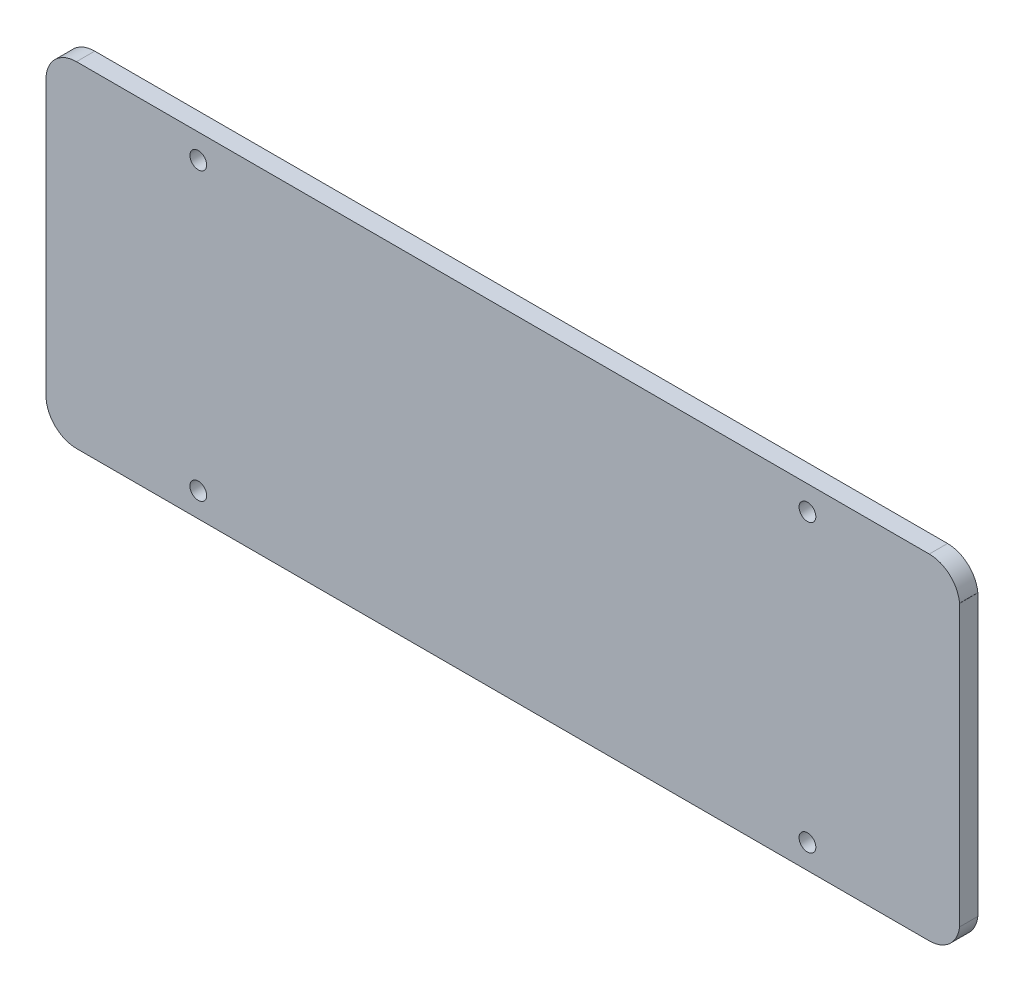
SolidWorks part; units mm, degrees
material "Aircraft Ply"
ref_plane "Front Plane" through (0, 0, 0) normal (0, 0, 1) x (1, 0, 0)
ref_plane "Top Plane" through (0, 0, 0) normal (0, 1, 0) x (1, 0, 0)
ref_plane "Right Plane" through (0, 0, 0) normal (1, 0, 0) x (0, 0, -1)
sketch "Sketch1" plane through (0, 0, 0) normal (0, 0, 1) x (1, 0, 0)
  line L0 (-75, 8) -> (75, 8) construction
  line L1 (-75, 0) -> (75, 0) construction
  line L8 (-75, 23) -> (-75, -23)
  line L9 (-44.3417, -23) -> (-25.6583, -23)
  line L10 (-14.3417, -23) -> (14.3417, -23)
  line L11 (25.6583, -23) -> (44.3417, -23)
  line L12 (75, -23) -> (75, 23)
  line L13 (44.3417, 23) -> (25.6583, 23)
  line L14 (14.3417, 23) -> (-14.3417, 23)
  line L15 (-25.6583, 23) -> (-44.3417, 23)
  line L16 (-75, 23) -> (-75, -23)
  line L17 (-44.3417, -23) -> (-25.6583, -23)
  line L18 (-14.3417, -23) -> (14.3417, -23)
  line L19 (25.6583, -23) -> (44.3417, -23)
  line L20 (75, -23) -> (75, 23)
  line L21 (44.3417, 23) -> (25.6583, 23)
  line L22 (14.3417, 23) -> (-14.3417, 23)
  line L23 (-25.6583, 23) -> (-44.3417, 23)
  line L30 (-75, -23) -> (-55.6583, -23)
  line L31 (-75, -23) -> (-55.6583, -23)
  line L32 (55.6583, -23) -> (75, -23)
  line L33 (55.6583, -23) -> (75, -23)
  line L34 (75, 23) -> (55.6583, 23)
  line L35 (75, 23) -> (55.6583, 23)
  line L36 (-55.6583, 23) -> (-75, 23)
  line L37 (-55.6583, 23) -> (-75, 23)
  line L38 (-54.075, 10.201) -> (-54.075, 5.799)
  line L39 (-61.925, 10.201) -> (-61.925, 5.799)
  line L40 (-29.925, 10.201) -> (-29.925, 5.799)
  line L41 (-22.075, 10.201) -> (-22.075, 5.799)
  line L42 (2.075, 10.201) -> (2.075, 5.799)
  line L43 (9.925, 10.201) -> (9.925, 5.799)
  line L44 (34.075, 10.201) -> (34.075, 5.799)
  line L45 (41.925, 10.201) -> (41.925, 5.799)
  line L46 (-13.925, -5.799) -> (-13.925, -10.201)
  line L47 (-6.075, -5.799) -> (-6.075, -10.201)
  line L48 (18.075, -5.799) -> (18.075, -10.201)
  line L49 (25.925, -5.799) -> (25.925, -10.201)
  line L50 (50.075, -5.799) -> (50.075, -10.201)
  line L51 (57.925, -5.799) -> (57.925, -10.201)
  line L52 (-45.925, -5.799) -> (-45.925, -10.201)
  line L53 (-38.075, -5.799) -> (-38.075, -10.201)
  circle A0 centre (-50, 23.5) radius 1.375 construction
  circle A1 centre (-20, 23.5) radius 1.375 construction
  circle A2 centre (20, 23.5) radius 1.375 construction
  circle A3 centre (50, 23.5) radius 1.375 construction
  circle A4 centre (50, -23.5) radius 1.375 construction
  circle A5 centre (20, -23.5) radius 1.375 construction
  circle A6 centre (-20, -23.5) radius 1.375 construction
  circle A7 centre (-50, -23.5) radius 1.375 construction
  circle A8 centre (-50, -23.5) radius 1.375
  circle A9 centre (-20, -23.5) radius 1.375
  circle A10 centre (20, -23.5) radius 1.375
  circle A11 centre (50, -23.5) radius 1.375
  circle A12 centre (50, 23.5) radius 1.375
  circle A13 centre (20, 23.5) radius 1.375
  circle A14 centre (-20, 23.5) radius 1.375
  circle A15 centre (-50, 23.5) radius 1.375
  circle A16 centre (-58, 8) radius 4.5
  circle A17 centre (-26, 8) radius 4.5
  circle A18 centre (6, 8) radius 4.5
  circle A19 centre (38, 8) radius 4.5
  circle A20 centre (-42, -8) radius 4.5
  circle A21 centre (-10, -8) radius 4.5
  circle A22 centre (22, -8) radius 4.5
  circle A23 centre (54, -8) radius 4.5
  arc A29 (-54, -23.5) -> (-55.6583, -23) centre (-55.6583, -26) ccw
  arc A30 (-54, -23.5) -> (-46, -23.5) centre (-50, -23.5) ccw
  arc A31 (-44.3417, -23) -> (-46, -23.5) centre (-44.3417, -26) ccw
  arc A32 (-24, -23.5) -> (-25.6583, -23) centre (-25.6583, -26) ccw
  arc A33 (-24, -23.5) -> (-16, -23.5) centre (-20, -23.5) ccw
  arc A34 (-14.3417, -23) -> (-16, -23.5) centre (-14.3417, -26) ccw
  arc A35 (16, -23.5) -> (14.3417, -23) centre (14.3417, -26) ccw
  arc A36 (16, -23.5) -> (24, -23.5) centre (20, -23.5) ccw
  arc A37 (25.6583, -23) -> (24, -23.5) centre (25.6583, -26) ccw
  arc A38 (46, -23.5) -> (44.3417, -23) centre (44.3417, -26) ccw
  arc A39 (46, -23.5) -> (54, -23.5) centre (50, -23.5) ccw
  arc A40 (55.6583, -23) -> (54, -23.5) centre (55.6583, -26) ccw
  arc A43 (54, 23.5) -> (55.6583, 23) centre (55.6583, 26) ccw
  arc A44 (54, 23.5) -> (46, 23.5) centre (50, 23.5) ccw
  arc A45 (44.3417, 23) -> (46, 23.5) centre (44.3417, 26) ccw
  arc A46 (24, 23.5) -> (25.6583, 23) centre (25.6583, 26) ccw
  arc A47 (24, 23.5) -> (16, 23.5) centre (20, 23.5) ccw
  arc A48 (14.3417, 23) -> (16, 23.5) centre (14.3417, 26) ccw
  arc A49 (-16, 23.5) -> (-14.3417, 23) centre (-14.3417, 26) ccw
  arc A50 (-16, 23.5) -> (-24, 23.5) centre (-20, 23.5) ccw
  arc A51 (-25.6583, 23) -> (-24, 23.5) centre (-25.6583, 26) ccw
  arc A52 (-46, 23.5) -> (-44.3417, 23) centre (-44.3417, 26) ccw
  arc A53 (-46, 23.5) -> (-54, 23.5) centre (-50, 23.5) ccw
  arc A54 (-55.6583, 23) -> (-54, 23.5) centre (-55.6583, 26) ccw
  arc A57 (-54, -23.5) -> (-55.6583, -23) centre (-55.6583, -26) ccw
  arc A58 (-54, -23.5) -> (-46, -23.5) centre (-50, -23.5) ccw
  arc A59 (-44.3417, -23) -> (-46, -23.5) centre (-44.3417, -26) ccw
  arc A60 (-24, -23.5) -> (-25.6583, -23) centre (-25.6583, -26) ccw
  arc A61 (-24, -23.5) -> (-16, -23.5) centre (-20, -23.5) ccw
  arc A62 (-14.3417, -23) -> (-16, -23.5) centre (-14.3417, -26) ccw
  arc A63 (16, -23.5) -> (14.3417, -23) centre (14.3417, -26) ccw
  arc A64 (16, -23.5) -> (24, -23.5) centre (20, -23.5) ccw
  arc A65 (25.6583, -23) -> (24, -23.5) centre (25.6583, -26) ccw
  arc A66 (46, -23.5) -> (44.3417, -23) centre (44.3417, -26) ccw
  arc A67 (46, -23.5) -> (54, -23.5) centre (50, -23.5) ccw
  arc A68 (55.6583, -23) -> (54, -23.5) centre (55.6583, -26) ccw
  arc A71 (54, 23.5) -> (55.6583, 23) centre (55.6583, 26) ccw
  arc A72 (54, 23.5) -> (46, 23.5) centre (50, 23.5) ccw
  arc A73 (44.3417, 23) -> (46, 23.5) centre (44.3417, 26) ccw
  arc A74 (24, 23.5) -> (25.6583, 23) centre (25.6583, 26) ccw
  arc A75 (24, 23.5) -> (16, 23.5) centre (20, 23.5) ccw
  arc A76 (14.3417, 23) -> (16, 23.5) centre (14.3417, 26) ccw
  arc A77 (-16, 23.5) -> (-14.3417, 23) centre (-14.3417, 26) ccw
  arc A78 (-16, 23.5) -> (-24, 23.5) centre (-20, 23.5) ccw
  arc A79 (-25.6583, 23) -> (-24, 23.5) centre (-25.6583, 26) ccw
  arc A80 (-46, 23.5) -> (-44.3417, 23) centre (-44.3417, 26) ccw
  arc A81 (-46, 23.5) -> (-54, 23.5) centre (-50, 23.5) ccw
  arc A82 (-55.6583, 23) -> (-54, 23.5) centre (-55.6583, 26) ccw
  dimension "D2" = 9
  dimension "D3" = 8
  dimension "D6" = 17
  dimension "D7" = 7.85
  dimension "D1" = 0
  dimension "D4" = 4
  dimension "D5" = 2
extrude "Boss-Extrude1" add sketch "Sketch1" along normal blind 3 contours A82 L37 L16 L31 A57 A58 A59 L17 A60 A61 A62 L18 A63 A64 A65 L19 A66 A67 A68 L33 L20 L35 A71 A72 A73 L21 A74 A75 A76 L22 A77 A78 A79 L23 A80 A81 A23 A22 A21 | L39 A16 | L38 A16 | L40 A17 | L41 A17 | L42 A18 | L43 A18 | L44 A19 | L45 A19 | L50 A23 | L51 A23 | L48 A22 | L49 A22 | L46 A21 | L47 A21 | L52 A20 | L53 A20 region at (0.1547, 0, 0) region at (-53.8437, 8, 0) region at (-62.1563, 8, 0) region at (-30.1563, 8, 0) region at (-21.8437, 8, 0) region at (1.8437, 8, 0) region at (10.1563, 8, 0) region at (33.8437, 8, 0) region at (42.1563, 8, 0) region at (-14.1563, -8, 0) region at (-5.8437, -8, 0) region at (17.8437, -8, 0) region at (26.1563, -8, 0) region at (49.8437, -8, 0) region at (58.1563, -8, 0) region at (-46.1563, -8, 0) region at (-37.8437, -8, 0)
sketch "Sketch2" plane through (0, 0, 3) normal (0, 0, 1) x (1, 0, 0)
  line L0 (-58, 8) -> (-42, -8) construction
  line L1 (-49.8527, 16.1473) -> (-33.8527, 0.1473)
  line L2 (-66.1473, -0.1473) -> (-50.1473, -16.1473)
  line L3 (-26, 8) -> (-10, -8) construction
  line L4 (-17.8527, 16.1473) -> (-1.8527, 0.1473)
  line L5 (-34.1473, -0.1473) -> (-18.1473, -16.1473)
  line L6 (22, -8) -> (6, 8) construction
  line L7 (13.8527, -16.1473) -> (-2.1473, -0.1473)
  line L8 (30.1473, 0.1473) -> (14.1473, 16.1473)
  line L9 (38, 8) -> (54, -8) construction
  line L10 (46.1473, 16.1473) -> (62.1473, 0.1473)
  line L11 (29.8527, -0.1473) -> (45.8527, -16.1473)
  arc A10 (-49.8527, 16.1473) -> (-66.1473, -0.1473) centre (-58, 8) ccw
  arc A11 (-50.1473, -16.1473) -> (-33.8527, 0.1473) centre (-42, -8) ccw
  arc A12 (-17.8527, 16.1473) -> (-34.1473, -0.1473) centre (-26, 8) ccw
  arc A13 (-18.1473, -16.1473) -> (-1.8527, 0.1473) centre (-10, -8) ccw
  arc A14 (13.8527, -16.1473) -> (30.1473, 0.1473) centre (22, -8) ccw
  arc A15 (14.1473, 16.1473) -> (-2.1473, -0.1473) centre (6, 8) ccw
  arc A16 (46.1473, 16.1473) -> (29.8527, -0.1473) centre (38, 8) ccw
  arc A17 (45.8527, -16.1473) -> (62.1473, 0.1473) centre (54, -8) ccw
  text T0 "      1" font "Century Gothic" height in points 18
  point P2 (-50, 0)
  point P7 (-18, 0)
  point P14 (14, 0)
  point P21 (46, 0)
sketch "Sketch3" plane through (0, 0, 0) normal (0, 0, 1) x (1, 0, 0)
  line L0 (75, -23) -> (75, 23) construction
  line L1 (-70, 27.5) -> (70, 27.5)
  line L2 (-75, 22.5) -> (-75, -22.5)
  line L3 (-70, -27.5) -> (70, -27.5)
  line L4 (75, 22.5) -> (75, -22.5)
  line L5 (-75, 23) -> (-75, -23) construction
  arc A0 (-46, 23.5) -> (-54, 23.5) centre (-50, 23.5) ccw construction
  arc A1 (-54, -23.5) -> (-46, -23.5) centre (-50, -23.5) ccw construction
  arc A2 (-75, -22.5) -> (-70, -27.5) centre (-70, -22.5) ccw
  arc A3 (70, -27.5) -> (75, -22.5) centre (70, -22.5) ccw
  arc A4 (70, 27.5) -> (75, 22.5) centre (70, 22.5) cw
  arc A5 (-70, 27.5) -> (-75, 22.5) centre (-70, 22.5) ccw
  circle A6 centre (-50, 23.5) radius 1.375
  circle A7 centre (50, 23.5) radius 1.375
  circle A8 centre (50, -23.5) radius 1.375
  circle A9 centre (-50, -23.5) radius 1.375
  dimension "D1" = 5
extrude "Boss-Extrude2" add sketch "Sketch3" along normal through all
equation "\"D6@Sketch1\"=(20+14)/2"
